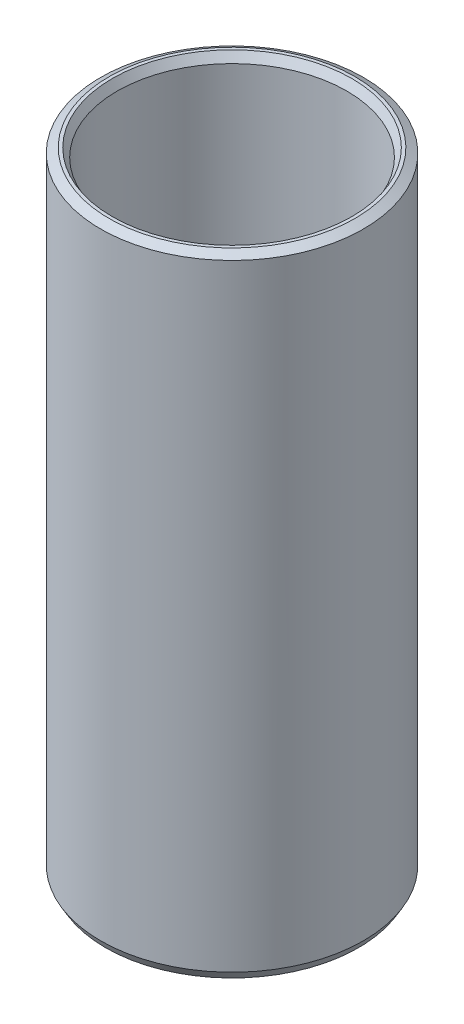
SolidWorks part; units mm, degrees
ref_plane "Front Plane" through (0, 0, 0) normal (0, 0, 1) x (1, 0, 0)
ref_plane "Top Plane" through (0, 0, 0) normal (0, 1, 0) x (1, 0, 0)
ref_plane "Right Plane" through (0, 0, 0) normal (1, 0, 0) x (0, 0, -1)
sketch "Sketch1" plane through (0, 0, 0) normal (0, 1, 0) x (1, 0, 0)
  circle A0 centre (0, 0) radius 37.5
  dimension "SLEEVE_OD" = 75
extrude "Boss-Extrude1" add sketch "Sketch1" along normal blind 179.7436
sketch "Sketch2" plane through (0, 0, 0) normal (0, 1, 0) x (1, 0, 0)
  circle A0 centre (0, 0) radius 32.7789
  dimension "BORE_D" = 65.5578
extrude "Cut-Extrude1" cut sketch "Sketch2" along normal through all
chamfer "Chamfer1" distance 1.3942 angle 60 4 edges at (0, 179.7436, 32.7789) (0, 0, 32.7789) (0, 0, 37.5) (0, 179.7436, 37.5) first distance on face at (0, 179.7436, 32.7789) first distance on face at (0, 0, 32.7789) first distance on face at (0, 179.7436, 37.5)
